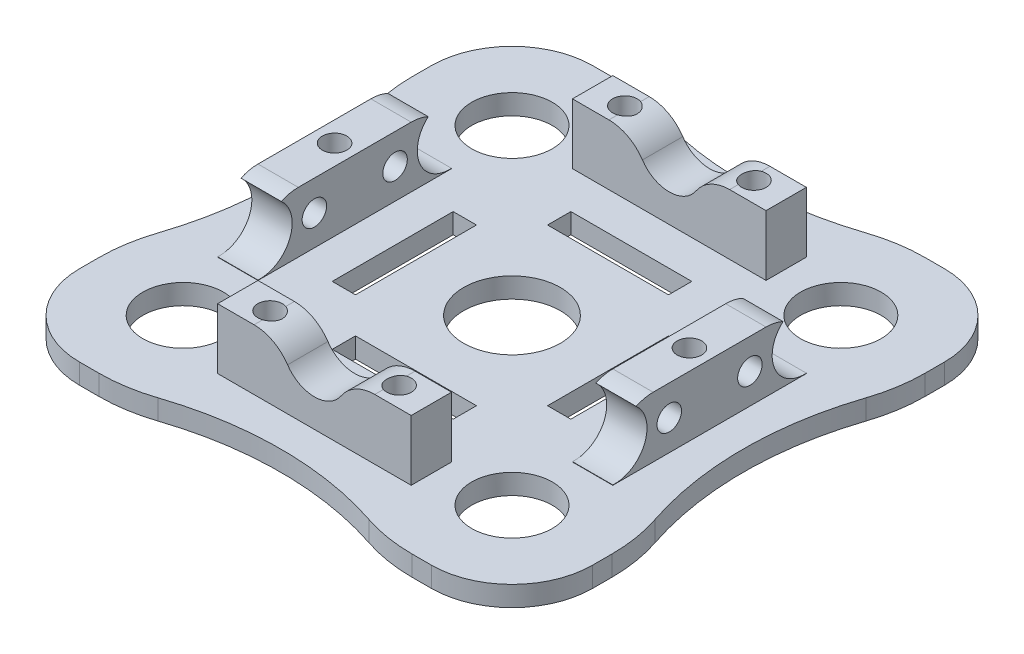
SolidWorks part; units mm, degrees
note: '?' marks a value the reader was unsure of.
ref_plane "Front" through (0, 0, 0) normal (0, 0, 1) x (1, 0, 0)
ref_plane "Top" through (0, 0, 0) normal (0, 1, 0) x (1, 0, 0)
ref_plane "Right" through (0, 0, 0) normal (1, 0, 0) x (0, 0, -1)
sketch "草图1" plane through (0, 0, 0) normal (0, 1, 0) x (1, 0, 0)
  line L0 (0, 24.7487) -> (0, 0) construction
  line L1 (31.8198, -31.8198) -> (15.8406, -31.8198)
  line L2 (31.8198, -31.8198) -> (31.8198, -15.8406)
  line L3 (31.8198, 31.8198) -> (15.8406, 31.8198)
  line L4 (-31.8198, -31.8198) -> (-31.8198, -15.8406)
  line L5 (31.8198, -31.8198) -> (-31.8198, 31.8198) construction
  line L6 (31.8198, 31.8198) -> (-31.8198, -31.8198) construction
  line L7 (0, 24.7487) -> (0, 70.2543) construction
  line L8 (-31.8198, 15.8406) -> (-31.8198, 31.8198)
  line L9 (31.8198, 15.8406) -> (31.8198, 31.8198)
  line L10 (-15.8406, -31.8198) -> (-31.8198, -31.8198)
  line L11 (-15.8406, 31.8198) -> (-31.8198, 31.8198)
  arc A0 (-15.8406, 31.8198) -> (15.8406, 31.8198) centre (0, 70.2543) ccw
  arc A1 (31.8198, 15.8406) -> (31.8198, -15.8406) centre (70.2543, 0) ccw
  arc A2 (15.8406, -31.8198) -> (-15.8406, -31.8198) centre (0, -70.2543) ccw
  arc A3 (-31.8198, -15.8406) -> (-31.8198, 15.8406) centre (-70.2543, 0) ccw
  point P0 (0, 0)
  point P23 (0, 0)
  dimension "D1" = 4
extrude "凸台-拉伸1" add sketch "草图1" along normal blind 2.5
fillet "圆角1" radius 10 1 edges at (31.8198, 1.25, 31.8198)
ref_axis "基准轴1" through (0, 27.9421, 0) along (0, 1, 0)?
fillet "圆角2" radius 10 1 edges at (31.8198, 1.25, -31.8198)
fillet "圆角3" radius 10 1 edges at (-31.8198, 1.25, -31.8198)
fillet "圆角4" radius 10 1 edges at (-31.8198, 1.25, 31.8198)
sketch "草图2" plane through (0, 2.5, 0) normal (0, 1, 0) x (1, 0, 0)
  line L0 (-31.8198, 15.8406) -> (-15.8406, 31.8198) construction
  line L1 (15.8406, -31.8198) -> (31.8198, -15.8406) construction
  line L2 (23.8302, -23.8302) -> (-23.8302, 23.8302) construction
  line L3 (-20.3878, 20.3878) -> (-15.8406, 31.8198) construction
  line L4 (-20.3878, 20.3878) -> (-31.8198, 15.8406) construction
  line L5 (-31.8198, 15.8406) -> (-23.8302, 23.8302) construction
  line L6 (-34.8639, 27.7928) -> (-27.7928, 34.8639) construction
  line L7 (15.8406, 31.8198) -> (-15.8406, 31.8198) construction
  line L12 (0, 31.8198) -> (0, 0) construction
  line L13 (-20.3878, 20.3878) -> (31.8198, 15.8406) construction
  line L14 (-50.7807, 30.9679) -> (-32.266, 49.4825) construction
  line L15 (7.5, 14.7945) -> (-7.5, 14.7945)
  line L16 (7.5, 14.7945) -> (7.5, 11.9069)
  line L17 (7.5, 11.9069) -> (-7.5, 11.9069)
  line L18 (-7.5, 14.7945) -> (-7.5, 11.9069)
  line L19 (7.5, 14.7945) -> (-7.5, 11.9069) construction
  line L20 (7.5, 11.9069) -> (-7.5, 14.7945) construction
  line L21 (-27.7928, 34.8639) -> (-46.8847, 53.9557) construction
  line L22 (-31.3283, 31.3283) -> (0, 0) construction
  line L23 (0, 0) -> (3.5355, 3.5355) construction
  circle A2 centre (-20.3878, 20.3878) radius 5
  circle A3 centre (-46.8847, 53.9557) radius 1.52
  circle A4 centre (-53.9557, 46.8847) radius 1.52
  point P11 (-31.3283, 31.3283)
  point P19 (0, 13.3507)
  dimension "D1" = 44.3049
  dimension "D2" = 28.8327
extrude "切除-拉伸1" cut sketch "草图2" against normal blind 49
fillet "圆角5" radius 20 1 edges at (-15.8406, 1.25, -31.8198)
fillet "圆角6" radius 20 1 edges at (-31.8198, 1.25, -15.8406)
pattern_circular "阵列(圆周)2" count 4 every 90 about axis through (0, 0, 0) along (0, 1, 0) of "切除-拉伸1"
sketch "草图3" plane through (0, 2.5, 0) normal (0, 1, 0) x (1, 0, 0)
  circle A0 centre (0, 0) radius 6
extrude "切除-拉伸2" cut sketch "草图3" against normal blind 49
sketch "草图4" plane through (0, 2.5, 0) normal (0, 1, 0) x (1, 0, 0)
fillet "圆角7" radius 20 1 edges at (31.8198, 1.25, 15.8406)
fillet "圆角8" radius 20 1 edges at (15.8406, 1.25, 31.8198)
fillet "圆角9" radius 20 1 edges at (-31.8198, 1.25, 15.8406)
fillet "圆角10" radius 20 1 edges at (-15.8406, 1.25, 31.8198)
fillet "圆角11" radius 20 1 edges at (15.8406, 1.25, -31.8198)
fillet "圆角12" radius 20 1 edges at (31.8198, 1.25, -15.8406)
ref_plane "基准面1" through (0, 10.5, 0) normal (0, 1, 0) x (1, 0, 0)
sketch "草图6" plane through (0, 2.5, 0) normal (0, 1, 0) x (1, 0, 0)
  line L0 (0, 0) -> (0, 22) construction
  line L1 (12, 24.5) -> (-12, 24.5)
  line L2 (12, 24.5) -> (12, 19.5)
  line L3 (12, 19.5) -> (-12, 19.5)
  line L4 (-12, 24.5) -> (-12, 19.5)
  line L5 (12, 24.5) -> (-12, 19.5) construction
  line L6 (12, 19.5) -> (-12, 24.5) construction
  line L7 (0, 22) -> (-28.9357, 22) construction
  line L8 (24.5, -12) -> (19.5, -12)
  line L9 (24.5, -12) -> (24.5, 12)
  line L10 (24.5, 12) -> (19.5, 12)
  line L11 (19.5, -12) -> (19.5, 12)
  line L12 (-12, -24.5) -> (-12, -19.5)
  line L13 (-12, -24.5) -> (12, -24.5)
  line L14 (12, -24.5) -> (12, -19.5)
  line L15 (-12, -19.5) -> (12, -19.5)
  line L16 (-24.5, 12) -> (-19.5, 12)
  line L17 (-24.5, 12) -> (-24.5, -12)
  line L18 (-24.5, -12) -> (-19.5, -12)
  line L19 (-19.5, 12) -> (-19.5, -12)
  point P0 (0, 22)
  point P8 (0, 0)
  point P23 (0, 0)
  dimension "D1" = 4
extrude "凸台-拉伸2" add sketch "草图6" along normal blind 7.5
sketch "草图7" plane through (0, 0, 0) normal (0, -1, 0) x (1, 0, 0)
  line L0 (0, 0) -> (-22, 0) construction
  line L1 (0, 0) -> (0, 22) construction
  line L2 (0, 22) -> (-8, 22) construction
  circle A0 centre (-22, 0) radius 1.52
  circle A2 centre (22, 0) radius 1.52
  circle A4 centre (0, -22) radius 1.52 [skipped]
  circle A5 centre (0, 22) radius 1.52 [skipped]
  circle A6 centre (-8, 22) radius 1.52
  circle A7 centre (8, 22) radius 1.52
  circle A8 centre (-8, -22) radius 1.52
  circle A9 centre (8, -22) radius 1.52
  point P13 (0, 0)
  dimension "D1" = 4
extrude "切除-拉伸4" cut sketch "草图7" against normal blind 16
sketch "草图8" plane through (0, 0, -24.5) normal (0, 0, -1) x (-1, 0, 0)
  line L0 (-12, 10) -> (12, 10) construction
  circle A0 centre (0, 10) radius 4
extrude "切除-拉伸5" cut sketch "草图8" against normal blind 57 contours A0
fillet "圆角13" radius 5 1 edges at (-4, 10, 22)
fillet "圆角14" radius 5 1 edges at (4, 10, 22)
fillet "圆角15" radius 5 1 edges at (-4, 10, -22)
fillet "圆角16" radius 5 1 edges at (4, 10, -22)
fillet "圆角17" radius 5 1 edges at (-22, 10, -12)
fillet "圆角18" radius 5 1 edges at (-22, 10, 12)
fillet "圆角19" radius 5 1 edges at (22, 10, 12)
fillet "圆角20" radius 5 1 edges at (22, 10, -12)
sketch "草图9" plane through (24.5, 0, 0) normal (1, 0, 0) x (0, 0, -1)
  line L0 (0, 0) -> (0, 11.9117) construction
  circle A0 centre (11.7582, 6.5361) radius 4.0015
  arc A1 (12, 5) -> (7, 10) centre (7, 5) ccw construction
  circle A2 centre (-11.7582, 6.5361) radius 4.0015
extrude "切除-拉伸6" cut sketch "草图9" against normal blind 57
sketch "草图10" plane through (-24.5, 0, 0) normal (-1, 0, 0) x (0, 0, 1)
  line L0 (0, 2.5) -> (0, 10) construction
  line L1 (-7, 10) -> (7, 10) construction
  line L2 (-12, 2.5) -> (12, 2.5) construction
  line L3 (-5, 6.25) -> (0, 6.25) construction
  circle A0 centre (-5, 6.25) radius 1.52
  circle A1 centre (5, 6.25) radius 1.52
extrude "切除-拉伸7" cut sketch "草图10" against normal blind 57
